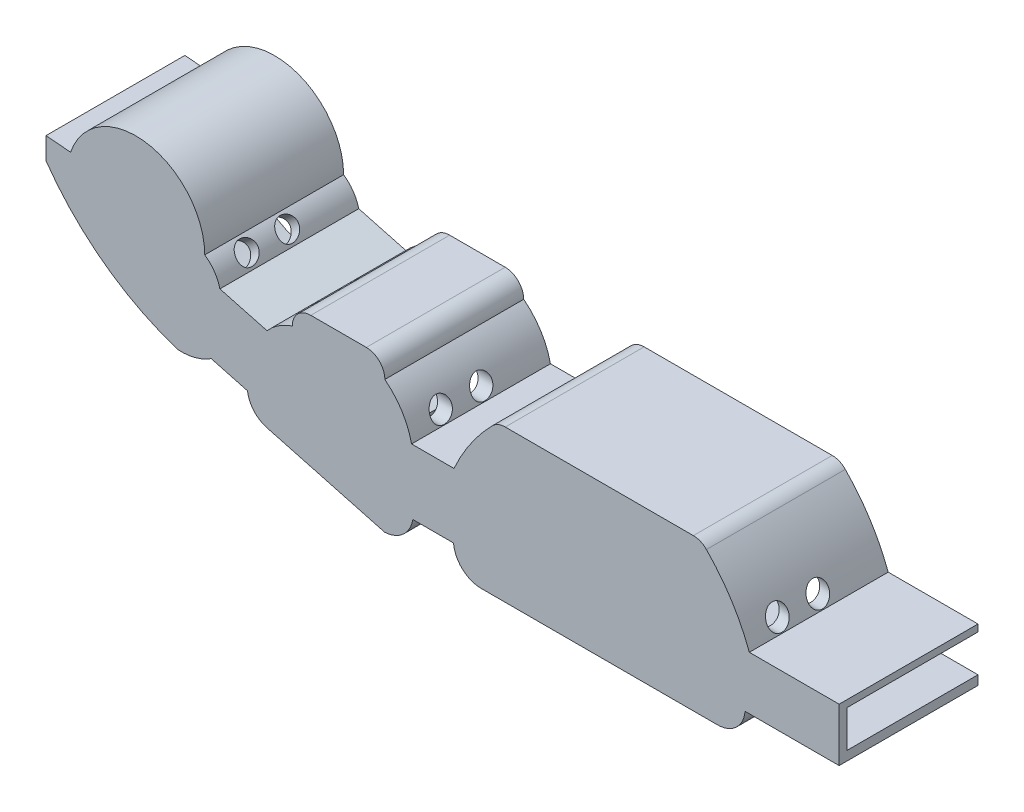
SolidWorks part; units mm, degrees
ref_plane "Front Plane" through (0, 0, 0) normal (0, 0, 1) x (1, 0, 0)
ref_plane "Top Plane" through (0, 0, 0) normal (0, 1, 0) x (1, 0, 0)
ref_plane "Right Plane" through (0, 0, 0) normal (1, 0, 0) x (0, 0, -1)
sketch "Sketch1" plane through (0, 0, 0) normal (0, 0, 1) x (1, 0, 0)
  line L23 (-11.1807, 10.652) -> (-11.4807, 9.152)
  line L24 (-11.4807, 9.152) -> (-11.7807, 10.652)
  line L25 (-11.7807, 10.652) -> (-12.4807, 10.652)
  line L36 (-12.4807, 10.652) -> (-12.7807, 9.152)
  line L40 (-12.7807, 9.152) -> (-13.0807, 10.652)
  line L41 (-13.0807, 10.652) -> (-13.7547, 10.652)
  line L47 (-13.7547, 10.652) -> (-14.0547, 9.152)
  line L48 (-14.0547, 9.152) -> (-14.3547, 10.652)
  line L49 (-14.3547, 10.652) -> (-15.0547, 10.652)
  line L50 (-15.0547, 10.652) -> (-15.3547, 9.152)
  line L51 (-15.3547, 9.152) -> (-15.6547, 10.652)
  line L52 (-15.6547, 10.652) -> (-16.3547, 10.652)
  line L53 (-16.3547, 10.652) -> (-16.6547, 9.152)
  line L54 (-16.6547, 9.152) -> (-16.9547, 10.652)
  line L55 (-16.9547, 10.652) -> (-17.6547, 10.652)
  line L56 (-17.6547, 10.652) -> (-17.9547, 9.152)
  line L57 (-17.9547, 9.152) -> (-18.2547, 10.652)
  line L58 (-18.2547, 10.652) -> (-18.9547, 10.652)
  line L59 (-18.9547, 10.652) -> (-19.2547, 9.152)
  line L60 (-19.2547, 9.152) -> (-19.5547, 10.652)
  line L61 (-19.5547, 10.652) -> (-20.2547, 10.652)
  line L62 (-20.2547, 10.652) -> (-20.5547, 9.152)
  line L63 (-20.5547, 9.152) -> (-20.8547, 10.652)
  line L64 (-20.8547, 10.652) -> (-21.5547, 10.652)
  line L65 (-21.5547, 10.652) -> (-21.8547, 9.152)
  line L66 (-21.8547, 9.152) -> (-22.1547, 10.652)
  line L67 (-22.1547, 10.652) -> (-22.8547, 10.652)
  line L68 (-22.8547, 10.652) -> (-23.1547, 9.152)
  line L69 (-23.1547, 9.152) -> (-23.4547, 10.652)
  line L70 (-23.4547, 10.652) -> (-24.1547, 10.652)
  line L71 (-24.1547, 10.652) -> (-24.4547, 9.152)
  line L72 (-24.4547, 9.152) -> (-24.7547, 10.652)
  line L73 (-24.7547, 10.652) -> (-25.4547, 10.652)
  line L74 (-25.4547, 10.652) -> (-25.7547, 9.152)
  line L75 (-25.7547, 9.152) -> (-26.0547, 10.652)
  line L76 (-26.0547, 10.652) -> (-26.7547, 10.652)
  line L77 (-26.7547, 10.652) -> (-27.0547, 9.152)
  line L78 (-27.0547, 9.152) -> (-27.3547, 10.652)
  line L79 (-27.3547, 10.652) -> (-28.0547, 10.652)
  line L80 (-28.0547, 10.652) -> (-28.3547, 9.152)
  line L167 (-55.8336, 10.6822) -> (-56.1336, 9.1822)
  line L170 (-57.7336, 10.6822) -> (-58.4336, 10.6822)
  line L171 (8.2817, 1.895) -> (-3.6348, 1.895)
  line L172 (-10.5067, 10.652) -> (-11.1807, 10.652)
  line L173 (-9.9067, 10.652) -> (-9.3532, 10.652)
  line L175 (-81.2436, 18.4578) -> (-81.5436, 19.5977)
  line L176 (-9.9067, 10.652) -> (-10.2067, 9.152)
  line L177 (-10.2067, 9.152) -> (-10.5067, 10.652)
  line L178 (-84.8421, 18.9938) -> (-85.1421, 17.6938)
  line L179 (-3.7183, -2.905) -> (8.2817, -2.905)
  line L180 (-2.7142, -4.105) -> (9.4817, -4.105)
  line L181 (-45.9381, 4.295) -> (-40.4408, 4.295)
  line L183 (9.4817, 2.795) -> (9.4817, -4.105)
  line L184 (8.2817, 1.895) -> (8.2817, -2.905)
  line L185 (-2.1578, 2.795) -> (9.4817, 2.795)
  line L186 (-89.2867, 9.2655) -> (-92.5842, 13.2092)
  line L187 (-57.1336, 10.6822) -> (-57.4336, 9.1822)
  line L188 (-78.6436, 17.8313) -> (-78.9436, 19.0854)
  line L189 (-69.6127, 0.2682) -> (-67.2052, -0.3779)
  line L190 (-93.3257, 12.3858) -> (-93.3257, 15.2174)
  line L191 (-63.026, -2.5288) -> (-50.4703, -5.8983)
  line L192 (-53.2596, 10.6822) -> (-53.5596, 9.1822)
  line L193 (-54.8596, 9.1822) -> (-55.1596, 10.6822)
  line L194 (-56.4336, 10.6822) -> (-57.1336, 10.6822)
  line L195 (-92.5842, 13.2092) -> (-92.5842, 13.9453)
  line L196 (-56.1336, 9.1822) -> (-56.4336, 10.6822)
  line L197 (-76.0436, 15.6755) -> (-76.3436, 17.4876)
  line L198 (-82.2448, 19.5875) -> (-82.5448, 18.3969)
  line L199 (-72.0187, 8.3687) -> (-64.2921, 6.2951)
  line L200 (-33.5547, 9.152) -> (-33.8579, 10.6577)
  line L201 (-53.8596, 10.6822) -> (-54.5596, 10.6822)
  line L202 (-82.5448, 18.3969) -> (-82.8448, 19.5298)
  line L203 (-53.1174, 10.6822) -> (-53.2596, 10.6822)
  line L204 (-86.4402, 16.8139) -> (-86.7402, 17.886)
  line L205 (-90.5408, 12.3858) -> (-92.1985, 13.5047)
  line L206 (-85.1421, 17.6938) -> (-85.4421, 18.7169)
  line L207 (-58.7336, 9.1822) -> (-59.0336, 10.6822)
  line L208 (-75.7436, 16.8755) -> (-76.0436, 15.6755)
  line L209 (-92.5842, 13.9453) -> (-92.1985, 13.5047)
  line L210 (-77.3436, 16.9603) -> (-77.6436, 18.4574)
  line L211 (-79.6436, 19.313) -> (-79.9436, 18.263)
  line L212 (-47.4928, 3.095) -> (-39.4928, 3.095)
  line L213 (-74.4436, 14.8576) -> (-74.7436, 12.8576)
  line L214 (-79.9436, 18.263) -> (-80.2436, 19.4536)
  line L215 (-87.4418, 17.2662) -> (-87.7418, 15.3662)
  line L216 (-51.804, 12.2025) -> (-59.004, 12.2025)
  line L217 (-53.5596, 9.1822) -> (-53.8596, 10.6822)
  line L218 (-80.9436, 19.5578) -> (-81.2436, 18.4578)
  line L219 (-86.1402, 18.3139) -> (-86.4402, 16.8139)
  line L220 (-73.1607, 2.4628) -> (-65.32, 0.3587)
  line L221 (-54.5596, 10.6822) -> (-54.8596, 9.1822)
  line L222 (-74.7436, 12.8576) -> (-75.0436, 15.955)
  line L223 (-77.0436, 18.0603) -> (-77.3436, 16.9603)
  line L224 (-87.7418, 15.3662) -> (-88.0418, 16.5999)
  line L225 (-45.7722, -4.105) -> (-40.5012, -4.105)
  line L226 (-93.3257, 15.2174) -> (-90.1372, 14.9459)
  line L227 (-39.4971, -2.905) -> (-47.5235, -2.905)
  line L228 (-57.4336, 9.1822) -> (-57.7336, 10.6822)
  line L229 (-78.3436, 18.8313) -> (-78.6436, 17.8313)
  line L230 (-83.5426, 19.4048) -> (-83.8426, 18.1477)
  line L231 (-55.1596, 10.6822) -> (-55.8336, 10.6822)
  line L232 (-64.6727, 7.6397) -> (-70.7852, 9.2801)
  line L233 (-59.1174, 10.6822) -> (-59.0336, 10.6822)
  line L234 (-64.479, -3.3191) -> (-49.4122, -7.3625)
  line L235 (-58.4336, 10.6822) -> (-58.7336, 9.1822)
  line L236 (-83.8426, 18.1477) -> (-84.1426, 19.2451)
  line L237 (-69.6127, 0.2682) -> (-71.91, 0.8847)
  line L238 (-29.6547, 9.152) -> (-29.9547, 10.652)
  line L239 (-28.3547, 9.152) -> (-28.6547, 10.652)
  line L240 (-30.6547, 10.652) -> (-30.9547, 9.152)
  line L241 (-28.6547, 10.652) -> (-29.3547, 10.652)
  line L242 (-29.3547, 10.652) -> (-29.6547, 9.152)
  line L243 (-31.2547, 10.652) -> (-31.9547, 10.652)
  line L244 (-30.9547, 9.152) -> (-31.2547, 10.652)
  line L245 (-29.9547, 10.652) -> (-30.6547, 10.652)
  line L246 (-31.9547, 10.652) -> (-32.2547, 9.152)
  line L247 (-32.5547, 10.652) -> (-33.2547, 10.652)
  line L248 (-33.2547, 10.652) -> (-33.5547, 9.152)
  line L249 (-32.2547, 9.152) -> (-32.5547, 10.652)
  line L250 (-33.7968, 12.2681) -> (-9.4143, 12.2681)
  line L251 (-36.4691, -6.2141) -> (-6.7463, -6.2141)
  line L252 (-36.913, -7.4141) -> (-6.3025, -7.4141)
  arc A66 (-2.7142, -4.105) -> (-6.3025, -7.4141) centre (-6.3025, -3.8141) cw
  arc A67 (-3.7183, -2.905) -> (-6.7463, -6.2141) centre (-6.7023, -3.2144) cw
  arc A69 (-7.343, 8.6822) -> (-9.3532, 10.652) centre (-10.3911, 7.5822) ccw
  arc A70 (-7.343, 8.6822) -> (-3.6348, 1.895) centre (-11.6135, 1.9424) cw
  arc A71 (-2.1578, 2.795) -> (-7.7202, 11.551) centre (-25.381, -5.8132) ccw
  arc A72 (-9.4143, 12.2681) -> (-7.7202, 11.551) centre (-9.4143, 9.9085) cw
  arc A73 (-73.7436, 11.2299) -> (-74.4436, 14.8576) centre (-81.7767, 11.5612) ccw
  arc A74 (-61.1174, 8.6822) -> (-64.2921, 6.2951) centre (-59.2158, 2.8486) ccw
  arc A75 (-33.7968, 12.2681) -> (-35.4909, 11.551) centre (-33.7968, 9.9085) ccw
  arc A76 (-86.7402, 17.886) -> (-87.4418, 17.2662) centre (-81.7767, 11.5612) ccw
  arc A77 (-39.4971, -2.905) -> (-36.4691, -6.2141) centre (-36.5131, -3.2144) ccw
  arc A78 (-93.3257, 12.3858) -> (-76.2211, -0.2669) centre (-65.9173, 31.5502) ccw
  arc A79 (-77.6436, 18.4574) -> (-78.3436, 18.8313) centre (-81.7767, 11.5612) ccw
  arc A80 (-81.5436, 19.5977) -> (-82.2448, 19.5875) centre (-81.7767, 11.5612) ccw
  arc A81 (-82.8448, 19.5298) -> (-83.5426, 19.4048) centre (-81.7767, 11.5612) ccw
  arc A82 (-59.004, 12.2025) -> (-61.404, 9.8025) centre (-59.004, 9.8025) ccw
  arc A83 (-50.4703, -5.8983) -> (-47.5235, -2.905) centre (-50.7823, -2.644) ccw
  arc A84 (-89.2867, 9.2655) -> (-76.663, 0.8179) centre (-68.5402, 26.6123) ccw
  arc A85 (-51.1174, 8.6822) -> (-53.1174, 10.6822) centre (-53.1174, 8.6822) ccw
  arc A86 (-59.1174, 10.6822) -> (-61.1174, 8.6822) centre (-59.1174, 8.6822) ccw
  arc A87 (-40.5012, -4.105) -> (-36.913, -7.4141) centre (-36.913, -3.8141) ccw
  arc A88 (-45.9381, 4.295) -> (-49.404, 9.8025) centre (-55.2924, 2.2526) ccw
  arc A89 (-78.9436, 19.0854) -> (-79.6436, 19.313) centre (-81.7767, 11.5612) ccw
  arc A90 (-84.1426, 19.2451) -> (-84.8421, 18.9938) centre (-81.7767, 11.5612) ccw
  arc A91 (-90.1372, 14.9459) -> (-72.7466, 12.1147) centre (-81.6779, 12.081) cw
  arc A92 (-75.0436, 15.955) -> (-75.7436, 16.8755) centre (-81.7767, 11.5612) ccw
  arc A93 (-76.663, 0.8179) -> (-73.1607, 2.4628) centre (-75.8865, 3.7157) ccw
  arc A94 (-85.4421, 18.7169) -> (-86.1402, 18.3139) centre (-81.7767, 11.5612) ccw
  arc A95 (-61.404, 9.8025) -> (-64.6727, 7.6397) centre (-59.122, 2.8022) ccw
  arc A96 (-35.3838, 9.9746) -> (-35.8681, 8.6822) centre (-33.9017, 8.6822) ccw
  arc A97 (-49.4122, -7.3625) -> (-45.7722, -4.105) centre (-49.6396, -3.446) ccw
  arc A98 (-88.0418, 16.5999) -> (-89.7314, 12.7286) centre (-81.7767, 11.5612) ccw
  arc A99 (-65.32, 0.3587) -> (-63.026, -2.5288) centre (-62.4468, 0.2864) ccw
  arc A100 (-72.0187, 8.3687) -> (-73.7436, 11.2299) centre (-76.0325, 7.8995) ccw
  arc A101 (-33.8579, 10.6577) -> (-35.3838, 9.9746) centre (-33.8814, 8.6645) ccw
  arc A102 (-80.2436, 19.4536) -> (-80.9436, 19.5578) centre (-81.7767, 11.5612) ccw
  arc A103 (-49.404, 9.8025) -> (-51.804, 12.2025) centre (-51.804, 9.8025) ccw
  arc A104 (-40.4408, 4.295) -> (-35.4909, 11.551) centre (-17.8301, -5.8132) cw
  arc A105 (-67.2052, -0.3779) -> (-64.479, -3.3191) centre (-63.784, 0.0591) ccw
  arc A106 (-76.3436, 17.4876) -> (-77.0436, 18.0603) centre (-81.7767, 11.5612) ccw
  arc A107 (-71.91, 0.8847) -> (-76.2211, -0.2669) centre (-75.8411, 6.9561) cw
  arc A108 (-47.4928, 3.095) -> (-51.1174, 8.6822) centre (-55.388, 1.9424) ccw
  arc A109 (-70.7852, 9.2801) -> (-72.7466, 12.1147) centre (-75.4933, 8.1183) ccw
  arc A110 (-35.8681, 8.6822) -> (-39.4928, 3.095) centre (-31.5976, 1.9424) ccw
  arc A111 (-89.7314, 12.7286) -> (-90.5408, 12.3858) centre (-83.2152, -3.7856) ccw
  point P92 (-21.3666, 12.2681)
  dimension "D14" = 12
  dimension "D18" = 4.8
  dimension "D19" = 6.9
  dimension "D20" = 11.9164
extrude "Walls" add sketch "Sketch1" along normal blind 16 contours L242 region at (-4.585, -5.6764, 0)
sketch "Sketch2" plane through (0, 0, 0) normal (0, 0, -1) x (-1, 0, 0)
  line L10 (70.7852, 9.2801) -> (64.6727, 7.6397)
  line L12 (70.7852, 9.2801) -> (64.6727, 7.6397)
  line L14 (59.004, 12.2025) -> (51.804, 12.2025)
  line L15 (2.1578, 2.795) -> (-9.4817, 2.795)
  line L16 (59.004, 12.2025) -> (51.804, 12.2025)
  line L17 (2.1578, 2.795) -> (-9.4817, 2.795)
  line L18 (-9.4817, 2.795) -> (-9.4817, -4.105)
  line L19 (45.9381, 4.295) -> (40.4408, 4.295)
  line L22 (45.9381, 4.295) -> (40.4408, 4.295)
  line L37 (-9.4817, 2.795) -> (-9.4817, -4.105)
  line L38 (-9.4817, -4.105) -> (2.7142, -4.105)
  line L39 (-9.4817, -4.105) -> (2.7142, -4.105)
  line L40 (33.7968, 12.2681) -> (9.4143, 12.2681)
  line L42 (33.7968, 12.2681) -> (9.4143, 12.2681)
  line L44 (6.3025, -7.4141) -> (36.913, -7.4141)
  line L47 (6.3025, -7.4141) -> (36.913, -7.4141)
  line L49 (40.5012, -4.105) -> (45.7722, -4.105)
  line L50 (40.5012, -4.105) -> (45.7722, -4.105)
  line L51 (49.4122, -7.3625) -> (64.479, -3.3191)
  line L52 (49.4122, -7.3625) -> (64.479, -3.3191)
  line L53 (67.2052, -0.3779) -> (71.91, 0.8847)
  line L54 (67.2052, -0.3779) -> (71.91, 0.8847)
  line L55 (93.3257, 12.3858) -> (93.3257, 15.2174)
  line L56 (93.3257, 12.3858) -> (93.3257, 15.2174)
  line L57 (93.3257, 15.2174) -> (90.1372, 14.9459)
  line L58 (93.3257, 15.2174) -> (90.1372, 14.9459)
  arc A16 (9.4143, 12.2681) -> (7.7202, 11.551) centre (9.4143, 9.9085) ccw
  arc A17 (9.4143, 12.2681) -> (7.7202, 11.551) centre (9.4143, 9.9085) ccw
  arc A18 (64.6727, 7.6397) -> (61.404, 9.8025) centre (59.122, 2.8022) ccw
  arc A19 (64.6727, 7.6397) -> (61.404, 9.8025) centre (59.122, 2.8022) ccw
  arc A20 (61.404, 9.8025) -> (59.004, 12.2025) centre (59.004, 9.8025) ccw
  arc A21 (61.404, 9.8025) -> (59.004, 12.2025) centre (59.004, 9.8025) ccw
  arc A22 (51.804, 12.2025) -> (49.404, 9.8025) centre (51.804, 9.8025) ccw
  arc A23 (51.804, 12.2025) -> (49.404, 9.8025) centre (51.804, 9.8025) ccw
  arc A24 (49.404, 9.8025) -> (45.9381, 4.295) centre (55.2924, 2.2526) ccw
  arc A25 (7.7202, 11.551) -> (2.1578, 2.795) centre (25.381, -5.8132) ccw
  arc A26 (7.7202, 11.551) -> (2.1578, 2.795) centre (25.381, -5.8132) ccw
  arc A27 (2.7142, -4.105) -> (6.3025, -7.4141) centre (6.3025, -3.8141) ccw
  arc A28 (2.7142, -4.105) -> (6.3025, -7.4141) centre (6.3025, -3.8141) ccw
  arc A29 (49.404, 9.8025) -> (45.9381, 4.295) centre (55.2924, 2.2526) ccw
  arc A30 (40.4408, 4.295) -> (35.4909, 11.551) centre (17.8301, -5.8132) ccw
  arc A31 (40.4408, 4.295) -> (35.4909, 11.551) centre (17.8301, -5.8132) ccw
  arc A32 (35.4909, 11.551) -> (33.7968, 12.2681) centre (33.7968, 9.9085) ccw
  arc A33 (35.4909, 11.551) -> (33.7968, 12.2681) centre (33.7968, 9.9085) ccw
  arc A34 (36.913, -7.4141) -> (40.5012, -4.105) centre (36.913, -3.8141) ccw
  arc A35 (36.913, -7.4141) -> (40.5012, -4.105) centre (36.913, -3.8141) ccw
  arc A54 (45.7722, -4.105) -> (49.4122, -7.3625) centre (49.6396, -3.446) ccw
  arc A55 (45.7722, -4.105) -> (49.4122, -7.3625) centre (49.6396, -3.446) ccw
  arc A56 (64.479, -3.3191) -> (67.2052, -0.3779) centre (63.784, 0.0591) ccw
  arc A57 (64.479, -3.3191) -> (67.2052, -0.3779) centre (63.784, 0.0591) ccw
  arc A58 (71.91, 0.8847) -> (76.2211, -0.2669) centre (75.8411, 6.9561) ccw
  arc A59 (71.91, 0.8847) -> (76.2211, -0.2669) centre (75.8411, 6.9561) ccw
  arc A60 (76.2211, -0.2669) -> (93.3257, 12.3858) centre (65.9173, 31.5502) ccw
  arc A61 (76.2211, -0.2669) -> (93.3257, 12.3858) centre (65.9173, 31.5502) ccw
  arc A62 (90.1372, 14.9459) -> (72.7466, 12.1147) centre (81.6779, 12.081) ccw
  arc A63 (90.1372, 14.9459) -> (72.7466, 12.1147) centre (81.6779, 12.081) ccw
  arc A64 (72.7466, 12.1147) -> (70.7852, 9.2801) centre (75.4933, 8.1183) ccw
  arc A65 (72.7466, 12.1147) -> (70.7852, 9.2801) centre (75.4933, 8.1183) ccw
  dimension "D1" = 0
extrude "Base" add sketch "Sketch2" along normal blind 1
sketch "Sketch3" [suppressed] plane through (0, 0, 0) normal (0, 0, 1) x (1, 0, 0)
  line L4 (-65.1711, 5.3832) -> (-63.3958, 4.9067) construction
  line L5 (-84.8697, 19.5134) -> (-85.1843, 17.3997) construction
  line L6 (-51.77, 3.095) -> (-68.5693, 3.095) construction
  line L7 (-68.5693, 6.2951) -> (-68.5693, 3.095) construction
  line L8 (-51.77, 3.095) -> (-54.6697, 3.095) construction
  line L9 (-68.5693, 6.2951) -> (-65.1711, 5.3832) construction
  line L10 (-56.4697, 3.095) -> (-54.6697, 3.095) construction
  line L11 (-80.595, 9.5224) -> (-82.2789, 9.9743)
  line L12 (-80.595, 9.5224) -> (-76.2959, 8.3687) construction
  line L13 (-91.8537, 12.2226) -> (-90.116, 11.8146)
  line L14 (-82.2789, 9.9743) -> (-90.116, 11.8146) construction
  line L15 (-40.77, 3.095) -> (-37.27, 3.095) construction
  line L16 (-3.6422, 1.595) -> (-7.1422, 1.595) construction
  line L17 (-40.77, 3.095) -> (-3.7183, 3.095) construction
  line L18 (-22.2442, 8.652) -> (-22.2442, 3.095) construction
  line L19 (-22.8547, 10.652) -> (-22.1547, 10.652) construction
  line L20 (-22.2442, 10.652) -> (-22.2442, 8.652) construction
  line L21 (-37.27, 3.095) -> (-34.1769, 3.095) construction
  line L22 (-11.7175, 3.095) -> (-7.1422, 1.595) construction
  arc A1 (-82.2789, 9.9743) -> (-90.116, 11.8146) centre (-86.0365, 11.58) ccw
  arc A2 (-91.8537, 12.2226) -> (-80.595, 9.5224) centre (-86.0443, 11.6231) cw
  arc A3 (-54.6697, 3.095) -> (-65.1711, 5.3832) centre (-60.1697, 3.095) ccw construction
  arc A4 (-84.5208, 19.4536) -> (-85.2208, 19.5578) centre (-86.0539, 11.5612) ccw construction
  arc A5 (-56.4697, 3.095) -> (-63.3958, 4.9067) centre (-60.1697, 3.095) ccw construction
  arc A6 (-3.6422, 1.595) -> (-7.343, 8.6822) centre (-11.6135, 1.9424) ccw construction
  arc A7 (-7.1422, 1.595) -> (-37.27, 3.095) centre (-22.9472, -12.5401) ccw construction
  arc A8 (-11.7175, 3.095) -> (-34.1769, 3.095) centre (-22.9472, -12.5401) ccw construction
  dimension "D1" = 11
  dimension "D2" = 2.137
  dimension "D3" = 7.4
  dimension "D8" = 38.5
  dimension "D4" = 3.5184
  dimension "D5" = 3.5
  dimension "D6" = 3.5
  dimension "D7" = 2
sketch "Sketch4" [suppressed] plane through (0, 0, 16) normal (0, 0, 1) x (1, 0, 0)
  line L7 (-69.5947, 0.3005) -> (-71.4824, -0.3779)
  line L10 (-71.4824, -0.3779) -> (-76.1872, 0.8847)
  line L11 (-76.1872, 0.8847) -> (-77.6773, 2.0433)
  line L12 (-40.77, 3.095) -> (-41.1043, 4.1128)
  line L13 (-41.1043, 4.1128) -> (-49.5364, 4.1128)
  line L16 (-67.7226, 6.3478) -> (-68.9499, 7.6397)
  line L17 (-68.9499, 7.6397) -> (-75.0624, 9.2801)
  line L18 (-75.0624, 9.2801) -> (-76.3177, 7.7352)
  line L19 (-49.5364, 4.1128) -> (-51.77, 3.095)
  line L20 (-40.7743, -2.905) -> (-41.0926, -4.1129)
  line L21 (-41.0926, -4.1129) -> (-49.3636, -4.1129)
  line L22 (-49.3636, -4.1129) -> (-51.8007, -2.905)
  arc A0 (-67.7226, 6.3478) -> (-76.3177, 7.7352) centre (-69.7742, 20.955) cw
  arc A1 (-69.5947, 0.3005) -> (-77.6773, 2.0433) centre (-76.3689, -11.5028) ccw
  arc A2 (-40.7743, -2.905) -> (-51.8007, -2.905) centre (-46.2875, -28.5004) ccw
  arc A3 (-40.77, 3.095) -> (-51.77, 3.095) centre (-46.27, 28.5687) cw
extrude "Joint Width" [suppressed] add sketch "Sketch4" against normal blind 16
ref_plane "SideAnchorPlane" through (0, 0, 2.5) normal (0, 0, 1) x (1, 0, 0)
ref_plane "CentralAnchorPlane" through (0, 0, 13) normal (0, 0, 1) x (1, 0, 0)
sketch "Sketch5" [suppressed] plane through (0, 0, 3) normal (0, 0, 1) x (1, 0, 0)
  line L0 (-76.2959, 8.3687) -> (-68.5693, 6.2951) construction
  line L1 (-76.592, 9.4835) -> (-67.8744, 7.144) construction
  line L2 (-77.4258, 10.7304) -> (-66.9487, 7.9187) construction
  line L3 (-76.592, 9.4835) -> (-88.7757, 4.7797)
  line L4 (-77.4258, 10.7304) -> (-90.1205, 5.8293)
  line L5 (-78.0158, 11.7317) -> (-91.096, 6.6818)
  line L6 (-76.2959, 8.3687) -> (-87.6359, 3.9906)
  line L7 (-78.0158, 11.7317) -> (-77.4258, 10.7304)
  line L9 (-76.592, 9.4835) -> (-76.0479, 8.9395)
  line L10 (-76.0479, 8.9395) -> (-76.2959, 8.3687)
  line L11 (-91.096, 6.6818) -> (-91.096, 6.0024)
  line L12 (-91.096, 6.0024) -> (-90.1205, 5.8293)
  line L13 (-88.7757, 4.7797) -> (-88.5883, 3.9906)
  line L14 (-88.5883, 3.9906) -> (-87.6359, 3.9906)
  arc A0 (-76.2959, 8.3687) -> (-78.0208, 11.2299) centre (-80.3097, 7.8995) ccw construction
  arc A1 (-65.3947, 8.6822) -> (-68.5693, 6.2951) centre (-63.493, 2.8486) ccw construction
  arc A2 (-76.2959, 8.3687) -> (-78.0208, 11.2299) centre (-80.3097, 7.8995) ccw construction
  arc A4 (-93.5639, 9.2655) -> (-80.9402, 0.8179) centre (-72.8174, 26.6123) ccw construction
  arc A5 (-93.5639, 9.2655) -> (-80.9402, 0.8179) centre (-72.8174, 26.6123) ccw construction
  dimension "D1" = 1
  dimension "D2" = 1.5
  dimension "D3" = 1.1466
  dimension "D4" = 1.1466
extrude "Boss-Extrude2" [suppressed] add sketch "Sketch5" along normal blind 1 and the other way blind 1 separate body
sketch "Sketch6" [suppressed] plane through (0, 0, 4) normal (0, 0, 1) x (1, 0, 0)
  line L1 (-87.6359, 3.9906) -> (-76.2959, 8.3687)
  line L4 (-78.0158, 11.7317) -> (-91.096, 6.6818)
  line L5 (-91.096, 6.6818) -> (-91.7792, 6.284)
  line L6 (-91.7792, 6.284) -> (-88.4163, 3.7031)
  line L7 (-88.4163, 3.7031) -> (-87.6359, 3.9906)
  line L8 (-78.0158, 11.7317) -> (-75.9969, 10.8669)
  line L9 (-75.9969, 10.8669) -> (-76.2959, 8.3687)
  arc A0 (-93.5639, 9.2655) -> (-80.9402, 0.8179) centre (-72.8174, 26.6123) ccw construction
extrude "Boss-Extrude4" [suppressed] add sketch "Sketch6" along normal blind 1
sketch "Sketch7" [suppressed] plane through (0, 0, 2) normal (0, 0, -1) x (-1, 0, 0)
  line L0 (87.6359, 3.9906) -> (90.1015, 4.9746)
  line L1 (90.1015, 4.9746) -> (91.096, 6.6818)
  line L2 (91.096, 6.6818) -> (78.0158, 11.7317)
  line L3 (78.0158, 11.7317) -> (76.2959, 10.4542)
  line L4 (76.2959, 10.4542) -> (76.2959, 8.3687)
  line L5 (76.2959, 8.3687) -> (87.6359, 3.9906)
extrude "Boss-Extrude5" [suppressed] add sketch "Sketch7" along normal blind 1
extrude "Boss-Extrude6" [suppressed] add sketch "Sketch3" along normal up to surface (16 mm away)
ref_plane "Plane3" through (-55, 0, 0) normal (1, 0, 0) x (0, 0, -1)
sketch "Sketch14" plane through (-55, 0, 0) normal (1, 0, 0) x (0, 0, -1)
  line L0 (-16, 3.095) -> (1, 3.095) construction
  line L1 (1, 2.795) -> (1, 11.551) construction
  line L2 (-16, 8.4472) -> (1, 8.4472) construction
  line L3 (-16, 11.551) -> (-16, 2.795) construction
  line L4 (-7.5, 8.4472) -> (-7.5, 3.095) construction
  line L6 (-7.5, 5.7711) -> (-16, 5.7711) construction
  line L7 (-16, 2.795) -> (-16, 3.095) construction
  line L8 (-16, 8.4472) -> (-16, 3.095) construction
  circle A4 centre (-12.75, 5.7711) radius 1.4
  circle A5 centre (-2.25, 5.7711) radius 1.4 construction
  circle A6 centre (-7.5, 5.7711) radius 1.4
  dimension "D1" = 2.8
  dimension "D2" = 5.25
  dimension "D3" = 0.3
extrude "Cut-Extrude2" cut sketch "Sketch14" along normal up to surface (16.4022 mm away) up to face at (-37.9858, 6.0868, 8)
sketch "Sketch15" plane through (0, 0, 0) normal (1, 0, 0) x (0, 0, -1)
  line L1 (-16, 2.795) -> (1, 2.795) construction
  line L5 (1, 2.795) -> (1, 5.795) construction
  line L6 (1, 2.795) -> (1, 11.551) construction
  line L7 (1, 5.795) -> (-16, 5.795) construction
  line L8 (-7.5, 5.795) -> (-7.5, 2.795) construction
  line L9 (-16, 11.551) -> (-16, 2.795) construction
  line L10 (-7.5, 4.295) -> (-16, 4.295) construction
  circle A4 centre (-12.75, 4.295) radius 1.4
  circle A5 centre (-2.25, 4.295) radius 1.4 construction
  circle A6 centre (-7.5, 4.295) radius 1.4
  dimension "D2" = 5.25
  dimension "D1" = 2.8
extrude "Cut-Extrude3" cut sketch "Sketch15" against normal up to surface (3.9894 mm away) up to face at (-5.0502, 5.5283, 8)
ref_plane "Plane4" through (-36.9966, -31.0193, 0) normal (0.7663, 0.6425, 0) x (0, 0, -1)
sketch "Sketch16" plane through (-36.9966, -31.0193, 0) normal (0.7663, 0.6425, 0) x (0, 0, -1)
  line L1 (-2.5, 57.2123) -> (-13, 57.2123) construction
  line L2 (-13, 55) -> (-13, -55) construction
  line L3 (-16, 56.0224) -> (-16, 52.5901) construction
  line L6 (-16, 54.3062) -> (1, 54.3062) construction
  line L7 (-7.75, 57.2123) -> (-13, 57.2123) construction
  line L12 (-16, 56.0224) -> (1, 56.0224) construction
  line L13 (-7.5, 56.0224) -> (-7.5, 52.5901) construction
  circle A0 centre (-2.5, 57.2123) radius 1.4 construction
  circle A1 centre (-13, 57.2123) radius 1.4 construction
  circle A2 centre (-12.75, 54.3062) radius 1.4
  circle A3 centre (-2.25, 54.3062) radius 1.4 construction
  circle A4 centre (-7.5, 54.3062) radius 1.4
  dimension "D1" = 2.8
  dimension "D4" = 5.25
  dimension "D5" = 2.8
  dimension "D3" = 5.25
extrude "Cut-Extrude4" cut sketch "Sketch16" against normal up to surface and the other way up to surface up to face at (-85.2899, 5.3613, 7.5) other way up to face at (-71.6357, 10.7875, 7.5)
ref_plane "Plane5" through (-59.5489, 21.7002, 0) normal (-0.9396, 0.3424, 0) x (0, 0, -1)
sketch "Sketch18" plane through (-59.5489, 21.7002, 0) normal (-0.9396, 0.3424, 0) x (0, 0, -1)
  line L0 (-16, 12.7682) -> (0, 12.7682) construction
  line L1 (-16, 14.0984) -> (-16, 11.8182) construction
  line L5 (-16, 11.8182) -> (1, 11.8182) construction
  line L6 (-7.5, 14.0984) -> (-7.5, 11.8182) construction
  line L14 (-7.5, 12.9583) -> (-16, 12.9583) construction
  circle A2 centre (-12.75, 12.9583) radius 1.4
  circle A3 centre (-2.25, 12.9583) radius 1.4 construction
  circle A4 centre (-7.5, 12.9583) radius 1.4
  dimension "D1" = 2.8
  dimension "D2" = 5.25
  dimension "D3" = 17
  dimension "D4" = 0.95
extrude "Cut-Extrude5" cut sketch "Sketch18" against normal up to surface (1.5569 mm away) up to face at (-62.804, 7.6207, 8)
sketch "Sketch19" plane through (0, 0, 0) normal (0, 0, 1) x (1, 0, 0)
  line L457 (-11.1807, 10.652) -> (-11.4807, 9.152)
  line L460 (-11.4807, 9.152) -> (-11.7807, 10.652)
  line L467 (-11.7807, 10.652) -> (-12.4807, 10.652)
  line L567 (-12.4807, 10.652) -> (-12.7807, 9.152)
  line L568 (-12.7807, 9.152) -> (-13.0807, 10.652)
  line L569 (-13.0807, 10.652) -> (-13.7547, 10.652)
  line L570 (-13.7547, 10.652) -> (-14.0547, 9.152)
  line L571 (-14.0547, 9.152) -> (-14.3547, 10.652)
  line L572 (-14.3547, 10.652) -> (-15.0547, 10.652)
  line L573 (-15.0547, 10.652) -> (-15.3547, 9.152)
  line L574 (-15.3547, 9.152) -> (-15.6547, 10.652)
  line L575 (-15.6547, 10.652) -> (-16.3547, 10.652)
  line L576 (-16.3547, 10.652) -> (-16.6547, 9.152)
  line L577 (-16.6547, 9.152) -> (-16.9547, 10.652)
  line L578 (-16.9547, 10.652) -> (-17.6547, 10.652)
  line L579 (-17.6547, 10.652) -> (-17.9547, 9.152)
  line L580 (-17.9547, 9.152) -> (-18.2547, 10.652)
  line L581 (-18.2547, 10.652) -> (-18.9547, 10.652)
  line L582 (-18.9547, 10.652) -> (-19.2547, 9.152)
  line L583 (-19.2547, 9.152) -> (-19.5547, 10.652)
  line L584 (-19.5547, 10.652) -> (-20.2547, 10.652)
  line L585 (-20.2547, 10.652) -> (-20.5547, 9.152)
  line L586 (-20.5547, 9.152) -> (-20.8547, 10.652)
  line L587 (-20.8547, 10.652) -> (-21.5547, 10.652)
  line L588 (-21.5547, 10.652) -> (-21.8547, 9.152)
  line L589 (-21.8547, 9.152) -> (-22.1547, 10.652)
  line L590 (-22.1547, 10.652) -> (-22.8547, 10.652)
  line L591 (-22.8547, 10.652) -> (-23.1547, 9.152)
  line L592 (-23.1547, 9.152) -> (-23.4547, 10.652)
  line L593 (-23.4547, 10.652) -> (-24.1547, 10.652)
  line L594 (-24.1547, 10.652) -> (-24.4547, 9.152)
  line L595 (-24.4547, 9.152) -> (-24.7547, 10.652)
  line L596 (-24.7547, 10.652) -> (-25.4547, 10.652)
  line L597 (-25.4547, 10.652) -> (-25.7547, 9.152)
  line L598 (-25.7547, 9.152) -> (-26.0547, 10.652)
  line L599 (-26.0547, 10.652) -> (-26.7547, 10.652)
  line L600 (-26.7547, 10.652) -> (-27.0547, 9.152)
  line L601 (-27.0547, 9.152) -> (-27.3547, 10.652)
  line L602 (-27.3547, 10.652) -> (-28.0547, 10.652)
  line L603 (-28.0547, 10.652) -> (-28.3547, 9.152)
  line L604 (-55.8336, 10.6822) -> (-56.1336, 9.1822)
  line L605 (-57.7336, 10.6822) -> (-58.4336, 10.6822)
  line L606 (8.2817, 1.895) -> (-3.6348, 1.895)
  line L607 (-10.5067, 10.652) -> (-11.1807, 10.652)
  line L608 (-9.9067, 10.652) -> (-9.3532, 10.652)
  line L609 (-81.2436, 18.4578) -> (-81.5436, 19.5977)
  line L610 (-9.9067, 10.652) -> (-10.2067, 9.152)
  line L611 (-10.2067, 9.152) -> (-10.5067, 10.652)
  line L612 (-84.8421, 18.9938) -> (-85.1421, 17.6938)
  line L613 (-3.7183, -2.905) -> (8.2817, -2.905)
  line L617 (8.2817, 1.895) -> (8.2817, -2.905)
  line L619 (-89.2867, 9.2655) -> (-92.5842, 13.2092)
  line L620 (-57.1336, 10.6822) -> (-57.4336, 9.1822)
  line L621 (-78.6436, 17.8313) -> (-78.9436, 19.0854)
  line L624 (-63.026, -2.5288) -> (-50.4703, -5.8983)
  line L625 (-53.2596, 10.6822) -> (-53.5596, 9.1822)
  line L626 (-54.8596, 9.1822) -> (-55.1596, 10.6822)
  line L627 (-56.4336, 10.6822) -> (-57.1336, 10.6822)
  line L628 (-92.5842, 13.2092) -> (-92.5842, 13.9453)
  line L629 (-56.1336, 9.1822) -> (-56.4336, 10.6822)
  line L630 (-76.0436, 15.6755) -> (-76.3436, 17.4876)
  line L631 (-82.2448, 19.5875) -> (-82.5448, 18.3969)
  line L632 (-72.0187, 8.3687) -> (-64.2921, 6.2951)
  line L633 (-33.5547, 9.152) -> (-33.8579, 10.6577)
  line L634 (-53.8596, 10.6822) -> (-54.5596, 10.6822)
  line L635 (-82.5448, 18.3969) -> (-82.8448, 19.5298)
  line L636 (-53.1174, 10.6822) -> (-53.2596, 10.6822)
  line L637 (-86.4402, 16.8139) -> (-86.7402, 17.886)
  line L638 (-90.5408, 12.3858) -> (-92.1985, 13.5047)
  line L639 (-85.1421, 17.6938) -> (-85.4421, 18.7169)
  line L640 (-58.7336, 9.1822) -> (-59.0336, 10.6822)
  line L641 (-75.7436, 16.8755) -> (-76.0436, 15.6755)
  line L642 (-92.5842, 13.9453) -> (-92.1985, 13.5047)
  line L643 (-77.3436, 16.9603) -> (-77.6436, 18.4574)
  line L644 (-79.6436, 19.313) -> (-79.9436, 18.263)
  line L645 (-47.4928, 3.095) -> (-39.4928, 3.095)
  line L646 (-74.4436, 14.8576) -> (-74.7436, 12.8576)
  line L647 (-79.9436, 18.263) -> (-80.2436, 19.4536)
  line L648 (-87.4418, 17.2662) -> (-87.7418, 15.3662)
  line L650 (-53.5596, 9.1822) -> (-53.8596, 10.6822)
  line L651 (-80.9436, 19.5578) -> (-81.2436, 18.4578)
  line L652 (-86.1402, 18.3139) -> (-86.4402, 16.8139)
  line L653 (-73.1607, 2.4628) -> (-65.32, 0.3587)
  line L654 (-54.5596, 10.6822) -> (-54.8596, 9.1822)
  line L655 (-74.7436, 12.8576) -> (-75.0436, 15.955)
  line L656 (-77.0436, 18.0603) -> (-77.3436, 16.9603)
  line L657 (-87.7418, 15.3662) -> (-88.0418, 16.5999)
  line L660 (-39.4971, -2.905) -> (-47.5235, -2.905)
  line L661 (-57.4336, 9.1822) -> (-57.7336, 10.6822)
  line L662 (-78.3436, 18.8313) -> (-78.6436, 17.8313)
  line L663 (-83.5426, 19.4048) -> (-83.8426, 18.1477)
  line L664 (-55.1596, 10.6822) -> (-55.8336, 10.6822)
  line L666 (-59.1174, 10.6822) -> (-59.0336, 10.6822)
  line L668 (-58.4336, 10.6822) -> (-58.7336, 9.1822)
  line L669 (-83.8426, 18.1477) -> (-84.1426, 19.2451)
  line L671 (-29.6547, 9.152) -> (-29.9547, 10.652)
  line L672 (-28.3547, 9.152) -> (-28.6547, 10.652)
  line L673 (-30.6547, 10.652) -> (-30.9547, 9.152)
  line L674 (-28.6547, 10.652) -> (-29.3547, 10.652)
  line L675 (-29.3547, 10.652) -> (-29.6547, 9.152)
  line L676 (-31.2547, 10.652) -> (-31.9547, 10.652)
  line L677 (-30.9547, 9.152) -> (-31.2547, 10.652)
  line L678 (-29.9547, 10.652) -> (-30.6547, 10.652)
  line L679 (-31.9547, 10.652) -> (-32.2547, 9.152)
  line L680 (-32.5547, 10.652) -> (-33.2547, 10.652)
  line L681 (-33.2547, 10.652) -> (-33.5547, 9.152)
  line L682 (-32.2547, 9.152) -> (-32.5547, 10.652)
  line L684 (-36.4691, -6.2141) -> (-6.7463, -6.2141)
  arc A206 (-3.7183, -2.905) -> (-6.7463, -6.2141) centre (-6.7023, -3.2144) cw
  arc A207 (-7.343, 8.6822) -> (-9.3532, 10.652) centre (-10.3911, 7.5822) ccw
  arc A208 (-7.343, 8.6822) -> (-3.6348, 1.895) centre (-11.6135, 1.9424) cw
  arc A211 (-73.7436, 11.2299) -> (-74.4436, 14.8576) centre (-81.7767, 11.5612) ccw
  arc A212 (-61.1174, 8.6822) -> (-64.2921, 6.2951) centre (-59.2158, 2.8486) ccw
  arc A214 (-86.7402, 17.886) -> (-87.4418, 17.2662) centre (-81.7767, 11.5612) ccw
  arc A215 (-39.4971, -2.905) -> (-36.4691, -6.2141) centre (-36.5131, -3.2144) ccw
  arc A217 (-77.6436, 18.4574) -> (-78.3436, 18.8313) centre (-81.7767, 11.5612) ccw
  arc A218 (-81.5436, 19.5977) -> (-82.2448, 19.5875) centre (-81.7767, 11.5612) ccw
  arc A219 (-82.8448, 19.5298) -> (-83.5426, 19.4048) centre (-81.7767, 11.5612) ccw
  arc A221 (-50.4703, -5.8983) -> (-47.5235, -2.905) centre (-50.7823, -2.644) ccw
  arc A222 (-89.2867, 9.2655) -> (-76.663, 0.8179) centre (-68.5402, 26.6123) ccw
  arc A223 (-51.1174, 8.6822) -> (-53.1174, 10.6822) centre (-53.1174, 8.6822) ccw
  arc A224 (-59.1174, 10.6822) -> (-61.1174, 8.6822) centre (-59.1174, 8.6822) ccw
  arc A227 (-78.9436, 19.0854) -> (-79.6436, 19.313) centre (-81.7767, 11.5612) ccw
  arc A228 (-84.1426, 19.2451) -> (-84.8421, 18.9938) centre (-81.7767, 11.5612) ccw
  arc A230 (-75.0436, 15.955) -> (-75.7436, 16.8755) centre (-81.7767, 11.5612) ccw
  arc A231 (-76.663, 0.8179) -> (-73.1607, 2.4628) centre (-75.8865, 3.7157) ccw
  arc A232 (-85.4421, 18.7169) -> (-86.1402, 18.3139) centre (-81.7767, 11.5612) ccw
  arc A234 (-35.3838, 9.9746) -> (-35.8681, 8.6822) centre (-33.9017, 8.6822) ccw
  arc A236 (-88.0418, 16.5999) -> (-89.7314, 12.7286) centre (-81.7767, 11.5612) ccw
  arc A237 (-65.32, 0.3587) -> (-63.026, -2.5288) centre (-62.4468, 0.2864) ccw
  arc A238 (-72.0187, 8.3687) -> (-73.7436, 11.2299) centre (-76.0325, 7.8995) ccw
  arc A239 (-33.8579, 10.6577) -> (-35.3838, 9.9746) centre (-33.8814, 8.6645) ccw
  arc A240 (-80.2436, 19.4536) -> (-80.9436, 19.5578) centre (-81.7767, 11.5612) ccw
  arc A244 (-76.3436, 17.4876) -> (-77.0436, 18.0603) centre (-81.7767, 11.5612) ccw
  arc A246 (-47.4928, 3.095) -> (-51.1174, 8.6822) centre (-55.388, 1.9424) ccw
  arc A248 (-35.8681, 8.6822) -> (-39.4928, 3.095) centre (-31.5976, 1.9424) ccw
  arc A249 (-89.7314, 12.7286) -> (-90.5408, 12.3858) centre (-83.2152, -3.7856) ccw
  point P210 (-21.3666, 12.2681)
  dimension "D6" = 4.8
  dimension "D21" = 12
  dimension "D22" = 11.9164
extrude "Cut-Extrude6" cut sketch "Sketch19" against normal up to surface (1 mm away) up to face at (-45.6188, 4.8771, -1)
sketch "Sketch20" plane through (0, 0, 0) normal (0, 0, 1) x (1, 0, 0)
  line L0 (-90.3793, 6.0116) -> (-87.9003, 8.4287)
  line L1 (-87.566, 8.0563) -> (-90.0302, 5.6536)
  line L2 (-87.9003, 8.4287) -> (-87.566, 8.0563)
  line L3 (-90.0302, 5.6536) -> (-90.3793, 6.0116)
  line L4 (-57.3025, -6.2401) -> (-56.215, -2.1876)
  line L5 (-78.6588, 2.1835) -> (-79.6904, -0.5519)
  line L6 (-55.7321, -2.3172) -> (-56.8196, -6.3697)
  line L7 (-56.8196, -6.3697) -> (-57.3025, -6.2401)
  line L8 (-55.7321, -2.3172) -> (-56.215, -2.1876)
  line L9 (-79.6904, -0.5519) -> (-79.2225, -0.7283)
  line L10 (-24.748, -4.1815) -> (-24.248, -4.1815)
  line L11 (-24.748, -4.1815) -> (-24.748, -10.1505)
  line L12 (-24.748, -10.1505) -> (-24.248, -10.1505)
  line L13 (-24.248, -4.1815) -> (-24.248, -10.1505)
  line L14 (-79.2225, -0.7283) -> (-78.1909, 2.0071)
  line L15 (-78.1909, 2.0071) -> (-78.6588, 2.1835)
  line L16 (-50.4809, -5.8986) -> (-63.0366, -2.5291) construction
  line L17 (-92.5842, 13.2092) -> (-76.663, 0.8179) construction
  dimension "D1" = 0.5
  dimension "D2" = 0.5
  dimension "D3" = 0.5
  dimension "D4" = 0.5
extrude "Cut-Extrude7" cut sketch "Sketch20" along normal blind 13 from offset 1
sketch "Sketch21" plane through (0, 0, 0) normal (0, 0, 1) x (1, 0, 0)
  line L0 (9.4817, 2.795) -> (9.4817, -4.105) construction
  line L3 (8.2817, -2.905) -> (9.4817, -2.905)
  line L4 (9.4817, 1.895) -> (9.4817, -2.905)
  line L5 (8.2817, -2.905) -> (8.2817, 1.895)
  line L6 (8.2817, 1.895) -> (9.4817, 1.895)
  dimension "D1" = 4.8
extrude "Cut-Extrude8" cut sketch "Sketch21" against normal up to surface and the other way up to surface up to face at (-46.5296, 10.7965, -1) other way up to face at (-46.5296, 10.7965, 16)
ref_plane "Plane6" through (0, 0, 16) normal (0, 0, 1) x (1, 0, 0)
sketch "Sketch22" plane through (0, 0, 16) normal (0, 0, 1) x (1, 0, 0)
  line L190 (-2.7142, -4.105) -> (9.4817, -4.105)
  line L191 (-45.9381, 4.295) -> (-40.4408, 4.295)
  line L192 (9.4817, 2.795) -> (9.4817, -4.105)
  line L194 (-2.1578, 2.795) -> (9.4817, 2.795)
  line L198 (-69.6127, 0.2682) -> (-67.2052, -0.3779)
  line L199 (-93.3257, 12.3858) -> (-93.3257, 15.2174)
  line L225 (-51.804, 12.2025) -> (-59.004, 12.2025)
  line L234 (-45.7722, -4.105) -> (-40.5012, -4.105)
  line L235 (-93.3257, 15.2174) -> (-90.1372, 14.9459)
  line L241 (-64.6727, 7.6397) -> (-70.7852, 9.2801)
  line L243 (-64.479, -3.3191) -> (-49.4122, -7.3625)
  line L246 (-69.6127, 0.2682) -> (-71.91, 0.8847)
  line L259 (-33.7968, 12.2681) -> (-9.4143, 12.2681)
  line L261 (-36.913, -7.4141) -> (-6.3025, -7.4141)
  arc A77 (-2.7142, -4.105) -> (-6.3025, -7.4141) centre (-6.3025, -3.8141) cw
  arc A81 (-2.1578, 2.795) -> (-7.7202, 11.551) centre (-25.381, -5.8132) ccw
  arc A82 (-9.4143, 12.2681) -> (-7.7202, 11.551) centre (-9.4143, 9.9085) cw
  arc A85 (-33.7968, 12.2681) -> (-35.4909, 11.551) centre (-33.7968, 9.9085) ccw
  arc A88 (-93.3257, 12.3858) -> (-76.2211, -0.2669) centre (-65.9173, 31.5502) ccw
  arc A92 (-59.004, 12.2025) -> (-61.404, 9.8025) centre (-59.004, 9.8025) ccw
  arc A97 (-40.5012, -4.105) -> (-36.913, -7.4141) centre (-36.913, -3.8141) ccw
  arc A98 (-45.9381, 4.295) -> (-49.404, 9.8025) centre (-55.2924, 2.2526) ccw
  arc A101 (-90.1372, 14.9459) -> (-72.7466, 12.1147) centre (-81.6779, 12.081) cw
  arc A105 (-61.404, 9.8025) -> (-64.6727, 7.6397) centre (-59.122, 2.8022) ccw
  arc A107 (-49.4122, -7.3625) -> (-45.7722, -4.105) centre (-49.6396, -3.446) ccw
  arc A113 (-49.404, 9.8025) -> (-51.804, 12.2025) centre (-51.804, 9.8025) ccw
  arc A114 (-40.4408, 4.295) -> (-35.4909, 11.551) centre (-17.8301, -5.8132) cw
  arc A115 (-67.2052, -0.3779) -> (-64.479, -3.3191) centre (-63.784, 0.0591) ccw
  arc A117 (-71.91, 0.8847) -> (-76.2211, -0.2669) centre (-75.8411, 6.9561) cw
  arc A119 (-70.7852, 9.2801) -> (-72.7466, 12.1147) centre (-75.4933, 8.1183) ccw
  point P62 (-21.3666, 12.2681)
extrude "Boss-Extrude7" add sketch "Sketch22" along normal blind 1
